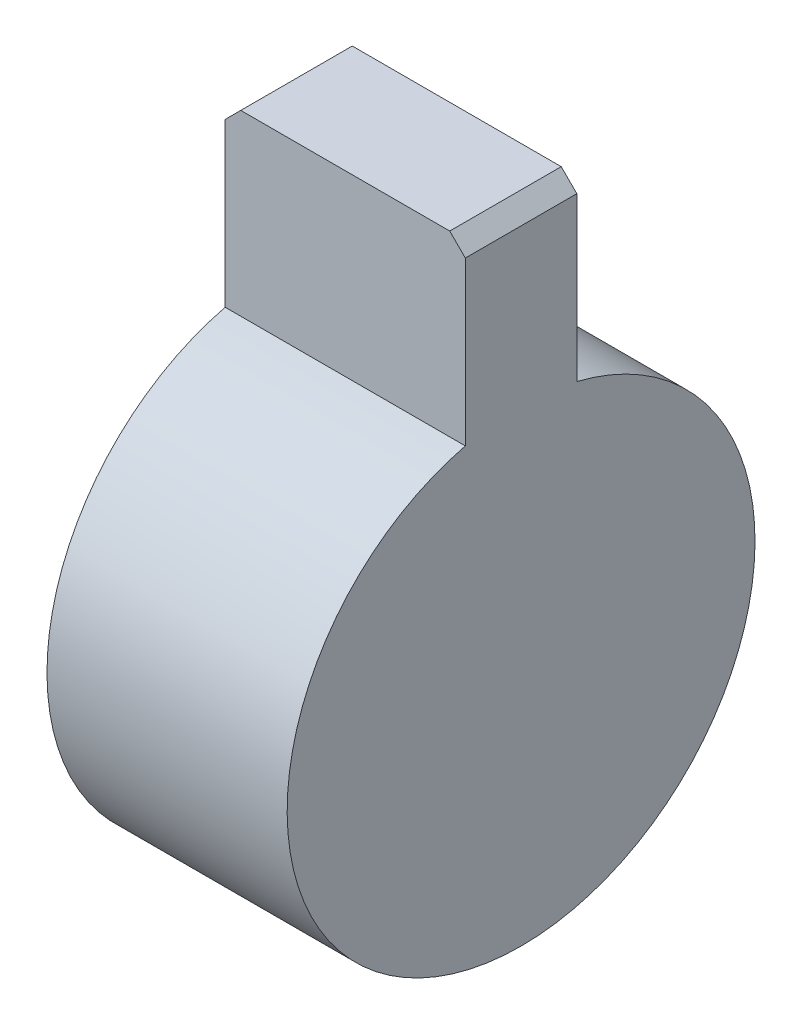
SolidWorks part; units mm, degrees
material "ABS"
ref_plane "Front Plane" through (0, 0, 0) normal (0, 0, 1) x (1, 0, 0)
ref_plane "Top Plane" through (0, 0, 0) normal (0, 1, 0) x (1, 0, 0)
ref_plane "Right Plane" through (0, 0, 0) normal (1, 0, 0) x (0, 0, -1)
sketch "Sketch1" plane through (0, 0, 0) normal (1, 0, 0) x (0, 0, -1)
  line L0 (-3.575, 14.5678) -> (-3.575, 26)
  line L1 (-3.575, 26) -> (3.575, 26)
  line L2 (3.575, 26) -> (3.575, 14.5678)
  line L3 (0, 26) -> (0, 0) construction
  arc A0 (-3.575, 14.5678) -> (3.575, 14.5678) centre (0, 0) ccw
  dimension "D1" = 30
  dimension "D2" = 26
  dimension "D3" = 7.15
extrude "Boss-Extrude1" add sketch "Sketch1" along normal blind 15.4 contours A0 L2 L1 L0
chamfer "Chamfer1" distance 1 angle 45 2 edges at (15.4, 26, 0) (0, 26, 0)
